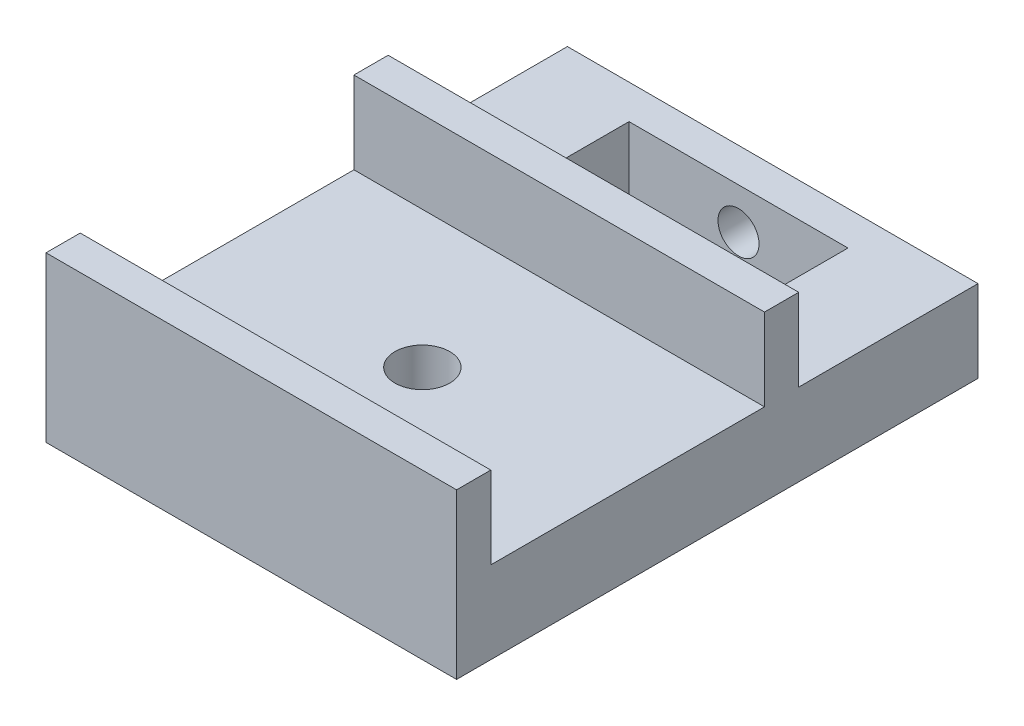
SolidWorks part; units mm, degrees
ref_plane "Front" through (0, 0, 0) normal (0, 0, 1) x (1, 0, 0)
ref_plane "Top" through (0, 0, 0) normal (0, 1, 0) x (1, 0, 0)
ref_plane "Right" through (0, 0, 0) normal (1, 0, 0) x (0, 0, -1)
sketch "Sketch1" plane through (0, 0, 0) normal (0, 1, 0) x (1, 0, 0)
  line L0 (0, -20) -> (0, -22.5)
  line L1 (0, 0) -> (-30, 0)
  line L2 (0, 0) -> (0, -20)
  line L3 (0, -20) -> (-30, -20)
  line L4 (-30, 0) -> (-30, -20)
  line L5 (0, -22.5) -> (-30, -22.5)
  line L6 (-30, -22.5) -> (-30, -20)
  line L7 (0, 0) -> (-7, 0)
  line L8 (-30, 0) -> (0, 0)
  line L9 (-30, 0) -> (-30, 2.5)
  line L10 (-30, 2.5) -> (0, 2.5)
  line L11 (0, 0) -> (0, 2.5)
  line L12 (-30, 0) -> (-23, 0)
  line L13 (-30, 2.5) -> (-30, 13.1)
  line L14 (-30, 13.1) -> (0, 13.1)
  line L15 (0, 13.1) -> (0, 2.5)
  line L16 (0, 13.1) -> (0, 15.6)
  line L17 (0, 15.6) -> (-30, 15.6)
  line L18 (-30, 15.6) -> (-30, 13.1)
  line L19 (-7, 0) -> (-7, 15.6)
  line L20 (-23, 0) -> (-23, 15.6)
  dimension "D1" = 20
  dimension "D2" = 2.5
  dimension "D3" = 2.5
  dimension "D4" = 30
  dimension "D5" = 7
  dimension "D6" = 7
  dimension "D7" = 10.6
  dimension "D8" = 2.5
extrude "Boss-Extrude1" add sketch "Sketch1" along normal blind 6 contours L1 L8 L4 L3 L2 | L6 L5 L0 L3 | L20 L1 L19 L10 | L19 L1 L11 L10 | L19 L10 L15 L14 | L19 L14 L16 L17 | L20 L14 L19 L17 | L14 L20 L17 L18 | L10 L20 L14 L13 | L8 L20 L10 L9 region at (-15, 0, 10) region at (-15, 0, 21.25) region at (-3.5, 0, -1.25) region at (-15, 0, -1.25) region at (-3.5, 0, -7.8) region at (-26.5, 0, -1.25) region at (-3.5, 0, -14.35) region at (-26.5, 0, -7.8) region at (-15, 0, -14.35) region at (-26.5, 0, -14.35)
extrude "Boss-Extrude2" add sketch "Sketch1<3>" along normal blind 12 contours L19 L1 L11 L10 | L20 L1 L19 L10 | L6 L5 L0 L3 | L8 L20 L10 L9 region at (-15, 0, 21.25) region at (-3.5, 0, -1.25) region at (-15, 0, -1.25) region at (-26.5, 0, -1.25)
sketch "Sketch1<3>" plane through (0, 0, 0) normal (0, 1, 0) x (1, 0, 0) same geometry as "Sketch1"
sketch "Sketch3" plane through (0, 0, -15.6) normal (0, 0, -1) x (-1, 0, 0)
  line L0 (30, 3) -> (23, 3)
  line L1 (30, 6) -> (30, 0) construction
  line L2 (23, 3) -> (15, 3)
  circle A0 centre (15, 3) radius 1.5
  dimension "D1" = 7
  dimension "D2" = 8
extrude "Cut-Extrude2" cut sketch "Sketch3" against normal blind 5 contours A0
sketch "Sketch4" plane through (0, 0, -2.5) normal (0, 0, -1) x (-1, 0, 0)
  line L0 (23, 3) -> (15, 3)
  line L1 (23, 6) -> (23, 0) construction
  line L3 (17.8868, 3) -> (16.4434, 5.5)
  line L4 (16.4434, 5.5) -> (13.5566, 5.5)
  line L5 (13.5566, 5.5) -> (12.1132, 3)
  line L6 (12.1132, 3) -> (13.5566, 0.5)
  line L7 (13.5566, 0.5) -> (16.4434, 0.5)
  line L8 (16.4434, 0.5) -> (17.8868, 3)
  circle A0 centre (15, 3) radius 2.5 construction
  dimension "D1" = 8
extrude "Cut-Extrude3" cut sketch "Sketch4" against normal blind 2.5 contours L7 L8 L3 L4 L5 L6 region at (-17.0989, 1.7882, -2.5)
ref_plane "Plane1" through (0, 0, 10) normal (0, 0, -1) x (-1, 0, 0)
sketch "Sketch2" plane through (0, 6, 0) normal (0, 1, 0) x (1, 0, 0)
  line L0 (-30, -10) -> (0, -10)
  line L1 (-30, 0) -> (-30, -20) construction
  line L2 (0, 0) -> (0, -20) construction
  circle A0 centre (-15, -10) radius 2
extrude "Cut-Extrude1" cut sketch "Sketch2" against normal through all contours L0 A0 | L0 A0 region at (-15, 6, 9.1512) region at (-15, 6, 10.8488)
